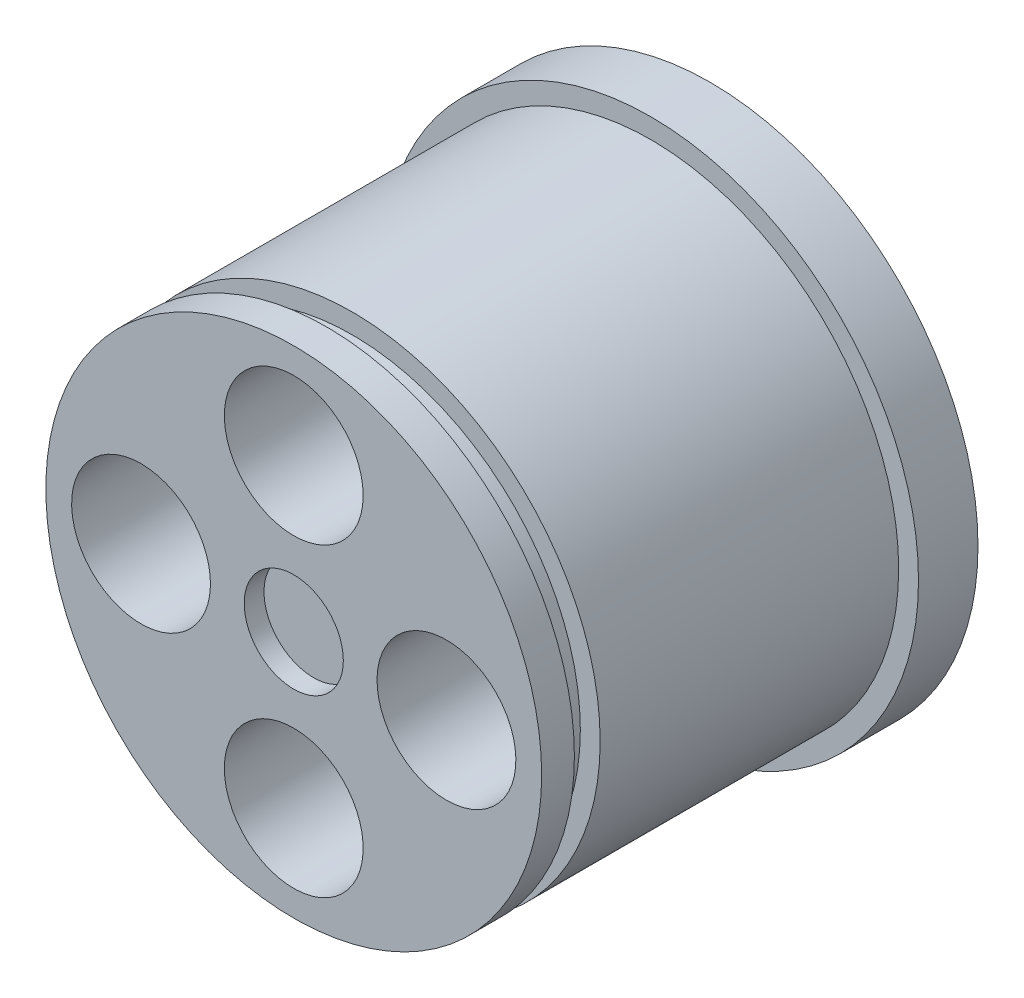
SolidWorks part; units mm, degrees
ref_plane "Front Plane" through (0, 0, 0) normal (0, 0, 1) x (1, 0, 0)
ref_plane "Top Plane" through (0, 0, 0) normal (0, 1, 0) x (1, 0, 0)
ref_plane "Right Plane" through (0, 0, 0) normal (1, 0, 0) x (0, 0, -1)
ref_axis "Z" through (0, 0, 10.5) along (0, 0, -1)
sketch "Sketch1" plane through (0, 0, 0) normal (0, 0, 1) x (1, 0, 0)
  circle A0 centre (0, 0) radius 12.5
  dimension "D1" = 25
extrude "Boss-Extrude1" add sketch "Sketch1" along normal blind 18
sketch "Sketch2" plane through (0, 0, 0) normal (0, 0, 1) x (1, 0, 0)
  circle A0 centre (0, 0) radius 13.5
  dimension "D1" = 27
extrude "Boss-Extrude2" add sketch "Sketch2" against normal blind 3
ref_plane "Plane1" through (0, 0, 15.7) normal (0, 0, 1) x (1, 0, 0)
sketch "Sketch3" plane through (0, 0, 15.7) normal (0, 0, 1) x (1, 0, 0)
  circle A0 centre (0, 0) radius 11.5
  circle A1 centre (0, 0) radius 58.2437
  dimension "D1" = 23
extrude "RetainingRingGroove" cut sketch "Sketch3" against normal blind 0.65 and the other way blind 0.65
sketch "Sketch4" plane through (0, 0, 18) normal (0, 0, 1) x (1, 0, 0)
  circle A0 centre (0, 0) radius 2.5
  dimension "D1" = 5
extrude "MagnetSlot" cut sketch "Sketch4" against normal blind 1
sketch "Sketch6" plane through (0, 0, 18) normal (0, 0, 1) x (1, 0, 0)
  line L0 (0, 0) -> (0, 7.7) construction
  line L2 (-1.4722, 10.25) -> (-2.9445, 7.7)
  line L3 (-2.9445, 7.7) -> (-1.4722, 5.15)
  line L4 (-1.4722, 5.15) -> (1.4722, 5.15)
  line L5 (1.4722, 5.15) -> (2.9445, 7.7)
  line L6 (2.9445, 7.7) -> (1.4722, 10.25)
  line L7 (1.4722, 10.25) -> (-1.4722, 10.25)
  circle A0 centre (0, 7.7) radius 2.55 construction
  point P3 (0, 0)
  dimension "D1" = 7.7
  dimension "D2" = 5.1
extrude "NutCut" cut sketch "Sketch6" against normal offset from surface (17 mm away) 4 up to face at (13.5, 0, -3)
sketch "Sketch7" plane through (0, 0, 18) normal (0, 0, 1) x (1, 0, 0)
  circle A0 centre (0, 7.7) radius 3.5
  dimension "D1" = 7
extrude "NutHole" cut sketch "Sketch7" against normal blind 15
sketch "Sketch8" plane through (0, 0, 18) normal (0, 0, 1) x (1, 0, 0)
  circle A0 centre (0, 7.7) radius 1.35
  dimension "D1" = 2.7
extrude "ScrewHole" cut sketch "Sketch8" against normal through all both and the other way through all
pattern_circular "CirPattern1" count 4 over 360 about axis through (0, 0, 10.5) along (0, 0, -1) of "MagnetSlot", "NutCut", "NutHole", "ScrewHole"
